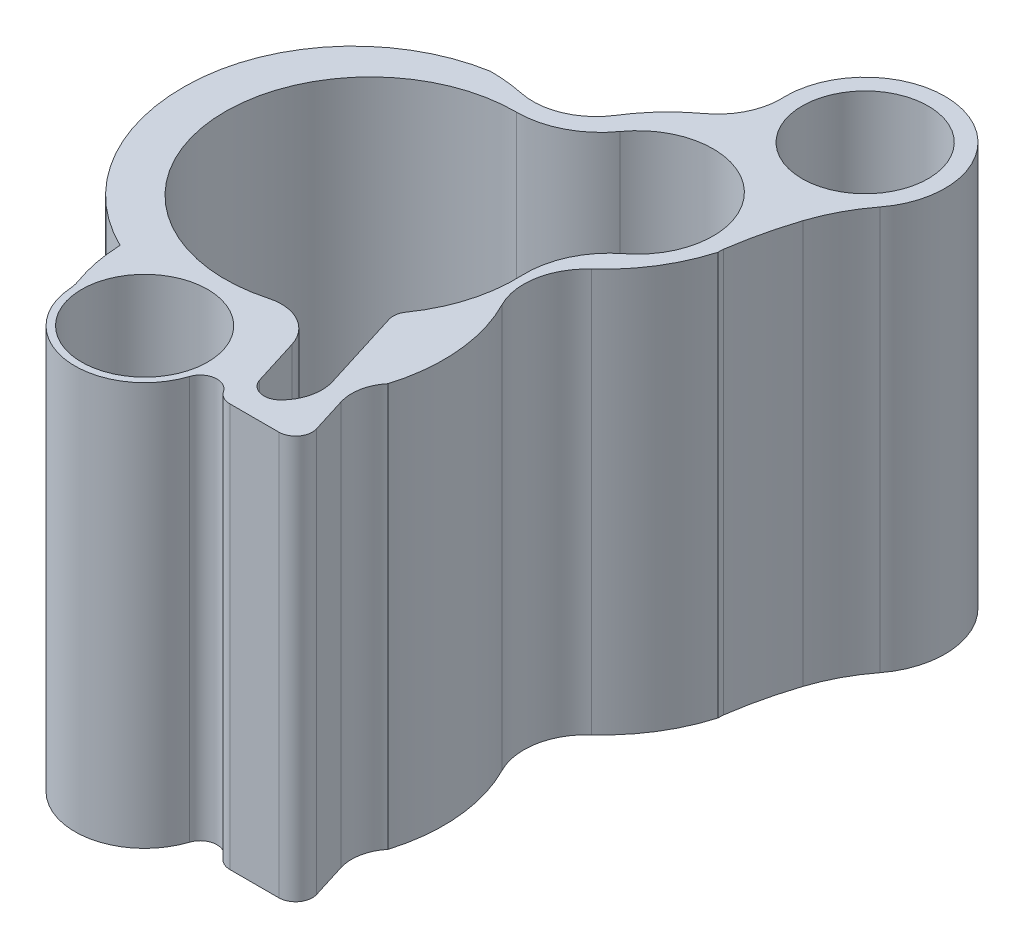
SolidWorks part; units mm, degrees
material "Markforged"
ref_plane "Front Plane" through (0, 0, 0) normal (0, 0, 1) x (1, 0, 0)
ref_plane "Top Plane" through (0, 0, 0) normal (0, 1, 0) x (1, 0, 0)
ref_plane "Right Plane" through (0, 0, 0) normal (1, 0, 0) x (0, 0, -1)
sketch "Sketch1" plane through (0, 0, 0) normal (0, 1, 0) x (1, 0, 0)
  line L0 (0, 17.0554) -> (0, -17.0554) construction
  line L1 (0, 0) -> (16.3625, 0) construction
  line L2 (5.7372, -9.3535) -> (8.3382, -17.6754)
  line L4 (11.8602, -12.8845) -> (13.7545, -18.9454)
  line L5 (13.7545, -18.9454) -> (7.4045, -18.9454)
  line L6 (6.6404, -16.5007) -> (7.4045, -18.9454)
  line L7 (8.3382, -17.6754) -> (12.027, -17.6754)
  line L8 (12.027, -17.6754) -> (8.6233, -6.7853)
  arc A0 (8.6233, -6.7853) -> (5.7372, -9.3535) centre (0, 0) ccw
  arc A1 (-6.188, 12.7228) -> (-6.188, -12.7228) centre (0, 0) ccw
  arc A2 (5.2705, 17.0554) -> (-5.2705, 17.0554) centre (0, 17.0554) ccw
  arc A4 (16.3625, -5.2705) -> (16.3625, 5.2705) centre (16.3625, 0) ccw
  circle A5 centre (0, 17.0554) radius 4.7625
  circle A6 centre (16.3625, 0) radius 4.7625
  arc A7 (5.2705, -17.0554) -> (-5.2705, -17.0554) centre (0, -17.0554) cw
  circle A8 centre (0, -17.0554) radius 4.7625
  arc A9 (5.2705, 17.0554) -> (16.3625, 5.2705) centre (-2.7565, -1.6119) cw
  arc A10 (16.3625, -5.2705) -> (11.8602, -12.8845) centre (-0.7121, -0.3122) cw
  arc A11 (6.6404, -16.5007) -> (5.2705, -17.0554) centre (-0.7121, -0.3122) cw
  arc A12 (-5.2705, -17.0554) -> (-6.188, -12.7228) centre (6.5049, -12.2983) cw
  arc A13 (-5.2705, 17.0554) -> (-6.188, 12.7228) centre (6.5049, 12.2983) ccw
  dimension "D1" = 21.9456
  dimension "D2" = 3.175
  dimension "D4" = 9.525
  dimension "D3" = 9.525
  dimension "D5" = 0.508
  dimension "D6" = 0.508
  dimension "D7" = 20.32
  dimension "D8" = 17.78
  dimension "D13" = 12.7
  dimension "D14" = 6.188
  dimension "D9" = 6.35
  dimension "D10" = 6.35
  dimension "D11" = 6.35
  dimension "D12" = 6.0609
  dimension "D15" = 1.27
  dimension "D16" = 1.27
  dimension "D17" = 1.27
extrude "Boss-Extrude2" add sketch "Sketch1" along normal blind 30.48
fillet "Fillet1" radius 3.175 9 edges at (5.7372, 15.24, 9.3535) (11.8602, 15.24, 12.8845) (5.2705, 15.24, -17.0554) (-5.2705, 15.24, -17.0554) (-5.2705, 15.24, 17.0554) (5.2705, 15.24, 17.0554) (16.3625, 15.24, 5.2705) (16.3625, 15.24, -5.2705) (-6.188, 15.24, -12.7228)
fillet "Fillet3" radius 1.27 2 edges at (13.7545, 15.24, 18.9454) (7.4045, 15.24, 18.9454)
fillet "Fillet4" radius 3.175 1 edges at (12.027, 15.24, 17.6754)
fillet "Fillet5" radius 1.27 1 edges at (8.3382, 15.24, 17.6754)
fillet "Fillet6" radius 1.27 2 edges at (6.6404, 15.24, 16.5007) (8.6233, 15.24, 6.7853)
sketch "Sketch2" plane through (0, 30.48, 0) normal (0, 1, 0) x (1, 0, 0)
  circle A5 centre (9.8968, 10.2919) radius 5.715
  circle A6 centre (9.8968, 10.2919) radius 6.985
  circle A8 centre (0, 0) radius 10.9728
  arc M14 (17.7713, 5.0787) -> (15.7312, 6.8206) centre (18.6199, 8.1382) cw
  arc M15 (15.7312, 6.8206) -> (6.6953, 16.376) centre (-2.7565, -1.6119) ccw
  arc M16 (6.6953, 16.376) -> (5.0999, 18.3854) centre (8.1722, 19.1866) cw
  arc M24 (2.9092, -10.5801) -> (8.9879, -6.2944) centre (0, 0) cw
  dimension "D1" = 11.43
  dimension "D2" = 1.27
extrude "Boss-Extrude9" add sketch "Sketch2" against normal up to surface (30.48 mm away) contours A6 A5 M14 M16 M15 region at (13.2604, 30.48, -15.0944) up to face at (16.3625, 0, 4.7625)
extrude "Cut-Extrude6" cut sketch "Sketch2<12>" against normal blind 30.48 contours A5 M24 M15 region at (9.5924, 30.48, -10.0648)
sketch "Sketch2<12>" plane through (0, 30.48, 0) normal (0, 1, 0) x (1, 0, 0) same geometry as "Sketch2"
fillet "Fillet9" radius 6.35 4 edges at (6.5804, 15.24, -16.4395) (15.8349, 15.24, -6.6137) (9.9724, 15.24, -4.5774) (4.1837, 15.24, -10.1439)
sketch "Sketch3" plane through (0, 30.48, 0) normal (0, 1, 0) x (1, 0, 0)
  line L0 (-7.5055, 11.9928) -> (-2.2961, 12.883)
  line L1 (4.7625, 17.0554) -> (9.7342, 17.2751)
  arc A0 (-7.5055, 11.9928) -> (9.7342, 17.2751) centre (1.4545, 13.5239) cw
  circle A1 centre (0, 17.0554) radius 4.7625 construction
  arc A2 (-2.2961, 12.883) -> (4.7625, 17.0554) centre (0, 17.0554) ccw
extrude "Cut-Extrude7" cut sketch "Sketch3" against normal through all both and the other way through all
sketch "Sketch4" plane through (0, 30.48, 0) normal (0, 1, 0) x (1, 0, 0)
  arc A0 (19.1055, 17.5548) -> (9.2013, 21.7865) centre (15.2215, 22.1706) ccw
  circle A1 centre (15.2215, 22.1706) radius 4.7625
  arc A4 (16.8659, 9.822) -> (9.7342, 17.2751) centre (9.8968, 10.2919) ccw construction
  arc A5 (4.7625, 17.0554) -> (9.189, 22.1706) centre (4.4182, 21.8263) ccw
  arc A6 (19.1055, 17.5548) -> (16.8659, 9.822) centre (45.2516, 5.7916) ccw
  arc M14 (16.8659, 9.822) -> (9.7342, 17.2751) centre (9.8968, 10.2919) ccw
  line M15 (9.7342, 17.2751) -> (4.7625, 17.0554)
  dimension "D1" = 1.27
  dimension "D2" = 9.525
extrude "Boss-Extrude11" add sketch "Sketch4" against normal up to surface (30.48 mm away) contours A6 A0 A5 A1 M15 M14 region at (17.4758, 30.48, -13.8361) up to face at (7.0011, 0, 6.0805)
fillet "Fillet10" radius 12.7 3 edges at (19.1055, 15.24, -17.5548) (-7.5055, 15.24, -11.9928) (4.7625, 15.24, -17.0554)
fillet "Fillet11" radius 12.7 1 edges at (-2.2961, 15.24, -12.883)
sketch "Sketch5" plane through (0, 30.48, 0) normal (0, 1, 0) x (1, 0, 0)
  line B0 (8.816, -7.4018) -> (10.7572, -13.6127)
  line B1 (6.7814, -12.6943) -> (7.8936, -16.253)
  line B2 (8.3382, -18.9454) -> (12.027, -18.9454)
  line B3 (13.2392, -17.2965) -> (12.4021, -14.6183)
  circle B4 centre (15.2215, 22.1706) radius 4.7625
  circle B5 centre (16.3625, 0) radius 4.7625
  circle B6 centre (0, -17.0554) radius 4.7625
  arc B7 (0.0582, 10.9726) -> (2.9092, -10.5801) centre (0, 0) ccw
  arc B8 (13.4063, 5.7814) -> (5.2524, 13.6222) centre (9.8968, 10.2919) ccw
  arc B9 (0.0582, 10.9726) -> (5.2524, 13.6222) centre (0.0919, 17.3226) ccw
  arc B10 (10.962, 0.4876) -> (13.4063, 5.7814) centre (17.3057, 0.7698) cw
  arc B11 (8.9879, -6.2944) -> (8.816, -7.4018) centre (10.0282, -7.023) ccw
  arc B12 (6.7814, -12.6943) -> (2.9092, -10.5801) centre (3.7509, -13.6415) ccw
  arc B13 (10.7572, -13.6127) -> (10.0251, -16.7503) centre (7.7268, -14.5598) cw
  arc B14 (10.0251, -16.7503) -> (7.8936, -16.253) centre (9.1058, -15.8741) cw
  arc B15 (8.9879, -6.2944) -> (10.962, 0.4876) centre (0, 0) ccw
  arc B16 (20.0035, 18.4931) -> (9.189, 22.1706) centre (15.2215, 22.1706) ccw
  arc B17 (9.189, 22.1706) -> (7.2496, 17.9711) centre (4.4182, 21.8263) cw
  arc B18 (7.2496, 17.9711) -> (4.0274, 14.5135) centre (14.7672, 7.7351) ccw
  arc B19 (4.0274, 14.5135) -> (-0.9762, 12.3941) centre (0, 17.0554) cw
  arc B20 (-3.5797, 12.6637) -> (-0.9762, 12.3941) centre (-3.5792, -0.0363) cw
  arc B21 (-3.5797, 12.6637) -> (-14.0765, 1.4183) centre (-1.4405, 0.1451) ccw
  arc B22 (-14.0765, 1.4183) -> (-6.188, -12.7228) centre (0, 0) ccw
  arc B23 (-6.188, -12.7228) -> (-5.4353, -16.6252) centre (6.5049, -12.2983) ccw
  arc B24 (-5.4353, -16.6252) -> (-5.2548, -17.462) centre (-8.4203, -17.707) cw
  arc B25 (-5.2548, -17.462) -> (5.0123, -18.6847) centre (0, -17.0554) ccw
  arc B26 (5.0123, -18.6847) -> (7.2792, -18.3764) centre (6.2201, -19.0773) cw
  arc B27 (7.2792, -18.3764) -> (8.3382, -18.9454) centre (8.3382, -17.6754) ccw
  arc B28 (12.027, -18.9454) -> (13.2392, -17.2965) centre (12.027, -17.6754) ccw
  arc B29 (12.4021, -14.6183) -> (12.9864, -11.6471) centre (15.4325, -13.6711) cw
  arc B30 (12.9864, -11.6471) -> (15.7931, -6.9233) centre (-0.7121, -0.3122) ccw
  arc B31 (15.7931, -6.9233) -> (17.8465, -5.0573) centre (18.7404, -8.1038) cw
  arc B32 (17.8465, -5.0573) -> (19.4644, 4.2611) centre (16.3625, 0) ccw
  arc B33 (19.4644, 4.2611) -> (16.8659, 9.822) centre (23.2016, 9.3949) cw
  arc B34 (20.0035, 18.4931) -> (17.9987, 14.695) centre (30.0708, 10.7511) ccw
  arc B35 (17.9987, 14.695) -> (16.8659, 9.822) centre (45.2516, 5.7916) ccw
sketch_block_instance "Block1-1"
sketch_block "Block1"
sketch "Sketch6" plane through (0, 30.48, 0) normal (0, 1, 0) x (1, 0, 0)
  line L0 (16.8659, 9.822) -> (16.3625, -4.7625)
  line L1 (16.3625, -4.7625) -> (12.9864, -11.6471)
  line L2 (12.9864, -11.6471) -> (20.4245, -6.7545)
  line L3 (20.4245, -6.7545) -> (23.856, 4.7625)
  line L4 (23.856, 4.7625) -> (16.8659, 9.822)
  circle A0 centre (16.3625, 0) radius 4.7625 construction
extrude "Cut-Extrude8" cut sketch "Sketch6" against normal through all both and the other way through all
fillet "Fillet12" radius 12.7 2 edges at (16.6909, 15.24, -4.7512)
